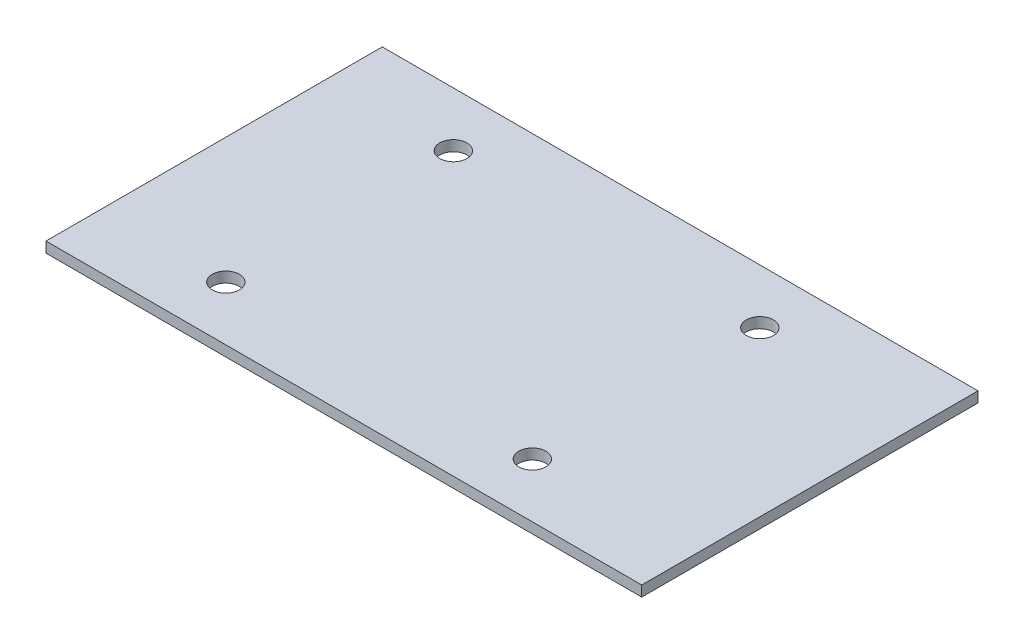
SolidWorks part; units mm, degrees
material "Cast Alloy Steel"
ref_plane "Front Plane" through (0, 0, 0) normal (0, 0, 1) x (1, 0, 0)
ref_plane "Top Plane" through (0, 0, 0) normal (0, 1, 0) x (1, 0, 0)
ref_plane "Right Plane" through (0, 0, 0) normal (1, 0, 0) x (0, 0, -1)
sketch "Sketch1" plane through (0, 0, 0) normal (0, 1, 0) x (1, 0, 0)
  line L1 (90, 50.8) -> (-90, 50.8)
  line L2 (90, 50.8) -> (90, -50.8)
  line L3 (90, -50.8) -> (-90, -50.8)
  line L4 (-90, 50.8) -> (-90, -50.8)
  line L5 (90, 50.8) -> (-90, -50.8) construction
  line L6 (90, -50.8) -> (-90, 50.8) construction
  circle A0 centre (-52.0875, 34.3735) radius 4.1
  circle A1 centre (40.5125, 34.3735) radius 4.1
  circle A2 centre (40.5125, -34.3735) radius 4.1
  circle A3 centre (-52.0875, -34.3735) radius 4.1
  point P0 (0, 0)
  point P18 (40.8623, 32.9903)
  point P21 (40.5125, 34.3735)
  dimension "D3" = 8.2
  dimension "D1" = 101.6
  dimension "D2" = 180
extrude "Boss-Extrude1" add sketch "Sketch1" along normal blind 3.175
